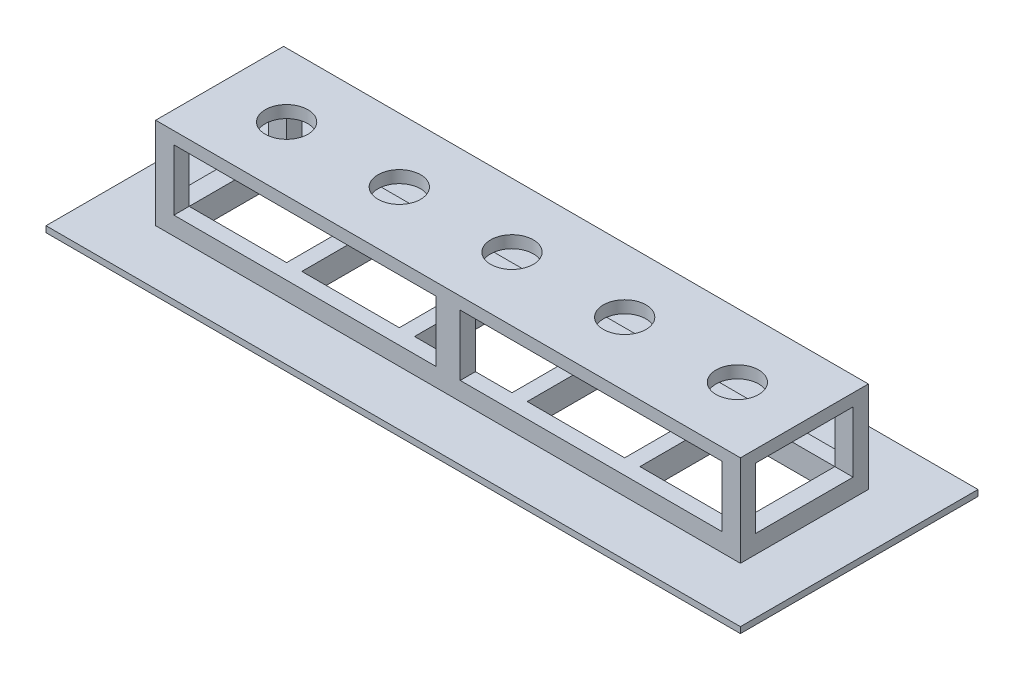
SolidWorks part; units mm, degrees
ref_plane "Front Plane" through (0, 0, 0) normal (0, 0, 1) x (1, 0, 0)
ref_plane "Top Plane" through (0, 0, 0) normal (0, 1, 0) x (1, 0, 0)
ref_plane "Right Plane" through (0, 0, 0) normal (1, 0, 0) x (0, 0, -1)
sketch "Sketch1" plane through (0, 0, 0) normal (0, 1, 0) x (1, 0, 0)
  line L1 (-48, 10.5) -> (48, 10.5)
  line L2 (-48, 10.5) -> (-48, -10.5)
  line L3 (-48, -10.5) -> (48, -10.5)
  line L4 (48, 10.5) -> (48, -10.5)
  line L5 (-48, 10.5) -> (48, -10.5) construction
  line L6 (-48, -10.5) -> (48, 10.5) construction
  point P0 (0, 0)
extrude "Boss-Extrude1" add sketch "Sketch1" along normal blind 3
sketch "Sketch2" plane through (0, 3, 0) normal (0, 1, 0) x (1, 0, 0)
  line L3 (-8, 8) -> (8, 8)
  line L4 (-8, 8) -> (-8, -8)
  line L5 (-45, 8) -> (-29, 8)
  line L6 (-45, 8) -> (-45, -8)
  line L7 (-45, -8) -> (-29, -8)
  line L8 (-29, 8) -> (-29, -8)
  line L9 (-45, 8) -> (-29, -8) construction
  line L10 (-45, -8) -> (-29, 8) construction
  line L11 (-26.5, 8) -> (-10.5, 8)
  line L12 (-26.5, 8) -> (-26.5, -8)
  line L13 (-26.5, -8) -> (-10.5, -8)
  line L14 (-10.5, 8) -> (-10.5, -8)
  line L15 (-26.5, 8) -> (-10.5, -8) construction
  line L16 (-26.5, -8) -> (-10.5, 8) construction
  line L17 (-8, -8) -> (8, -8)
  line L20 (8, 8) -> (8, -8)
  line L21 (-8, 8) -> (8, -8) construction
  line L22 (-8, -8) -> (8, 8) construction
  line L32 (10.5, 8) -> (26.5, 8)
  line L33 (10.5, 8) -> (10.5, -8)
  line L34 (10.5, -8) -> (26.5, -8)
  line L35 (26.5, 8) -> (26.5, -8)
  line L36 (10.5, 8) -> (26.5, -8) construction
  line L37 (10.5, -8) -> (26.5, 8) construction
  line L39 (29, 8) -> (45, 8)
  line L40 (29, 8) -> (29, -8)
  line L41 (29, -8) -> (45, -8)
  line L42 (45, 8) -> (45, -8)
  line L43 (29, 8) -> (45, -8) construction
  line L44 (29, -8) -> (45, 8) construction
  dimension "D1" = 16
  dimension "D2" = 16
  dimension "D3" = 16
  dimension "D4" = 16
  dimension "D5" = 16
  dimension "D6" = 16
  dimension "D7" = 16
  dimension "D8" = 16
  dimension "D9" = 16
  dimension "D10" = 16
extrude "Cut-Extrude3" cut sketch "Sketch2" against normal blind 7 and the other way blind 7
sketch "Sketch5" plane through (0, 3, 0) normal (0, 1, 0) x (1, 0, 0)
  line L0 (-45, 8) -> (-45, 10.5)
  line L1 (48, 10.5) -> (-48, 10.5) construction
  line L2 (-45, -8) -> (-45, -10.5)
  line L4 (-48, -10.5) -> (48, -10.5) construction
  line L5 (-48, 10.5) -> (-45, 10.5)
  line L6 (-48, 10.5) -> (-48, 8)
  line L7 (-48, 8) -> (-45, 8)
  line L8 (-45, 10.5) -> (-45, 8)
  line L9 (-48, 10.5) -> (-45, 8) construction
  line L10 (-48, 8) -> (-45, 10.5) construction
  line L11 (45, 8) -> (45, 10.5)
  line L12 (-48, 10.5) -> (-48, -10.5) construction
  line L13 (45, -8) -> (48, -8)
  line L14 (-48, -8) -> (-45, -8)
  line L15 (-48, -8) -> (-48, -10.5)
  line L16 (-48, -10.5) -> (-45, -10.5)
  line L17 (-45, -8) -> (-45, -10.5)
  line L18 (-48, -8) -> (-45, -10.5) construction
  line L19 (-48, -10.5) -> (-45, -8) construction
  line L20 (48, -10.5) -> (48, 10.5) construction
  line L21 (-8, 8) -> (8, 8) construction
  line L22 (45, 10.5) -> (48, 10.5)
  line L23 (45, 10.5) -> (45, 8)
  line L24 (45, 8) -> (48, 8)
  line L25 (48, 10.5) -> (48, 8)
  line L26 (45, 10.5) -> (48, 8) construction
  line L27 (45, 8) -> (48, 10.5) construction
  line L28 (0, -10.5) -> (0, -8)
  line L29 (45, -8) -> (48, -8)
  line L30 (45, -8) -> (45, -10.5)
  line L31 (45, -10.5) -> (48, -10.5)
  line L32 (48, -8) -> (48, -10.5)
  line L33 (45, -8) -> (48, -10.5) construction
  line L34 (45, -10.5) -> (48, -8) construction
  line L35 (-2, 10.5) -> (2, 10.5)
  line L36 (-2, 10.5) -> (-2, 8)
  line L37 (-2, 8) -> (2, 8)
  line L38 (2, 10.5) -> (2, 8)
  line L39 (-2, 10.5) -> (2, 8) construction
  line L40 (-2, 8) -> (2, 10.5) construction
  line L41 (8, -8) -> (-8, -8) construction
  line L42 (-2, -8) -> (2, -8)
  line L43 (-2, -8) -> (-2, -10.5)
  line L44 (-2, -10.5) -> (2, -10.5)
  line L45 (2, -8) -> (2, -10.5)
  line L46 (-2, -8) -> (2, -10.5) construction
  line L47 (-2, -10.5) -> (2, -8) construction
  point P9 (-46.5, 9.25)
  point P10 (-46.5, -9.25)
  point P21 (46.5, 9.25)
  point P29 (46.5, -9.25)
  point P32 (0, -9.25)
  point P38 (0, 9.25)
  line M37 (48, -10.5) -> (48, 10.5)
  line M38 (48, 10.5) -> (-48, 10.5)
  line M39 (-48, 10.5) -> (-48, -10.5)
  line M40 (-48, -10.5) -> (48, -10.5)
extrude "Boss-Extrude5" add sketch "Sketch5" along normal blind 10 contours L7 L0 M39 M38 | L14 L2 M39 M40 | L11 L24 M37 M38 | L13 L30 M40 M37 | L36 L35 L38 L37 | L43 L42 L45 L44 region at (-46.5, 3, -9.25) region at (-46.5, 3, 9.25) region at (46.5, 3, -9.25) region at (46.5, 3, 9.25)
sketch "Sketch6" plane through (0, 13, 0) normal (0, 1, 0) x (1, 0, 0)
  line L1 (-48, 10.5) -> (48, 10.5)
  line L2 (-48, 10.5) -> (-48, -10.5)
  line L3 (-48, -10.5) -> (48, -10.5)
  line L4 (48, 10.5) -> (48, -10.5)
  line L5 (-48, 10.5) -> (48, -10.5) construction
  line L6 (-48, -10.5) -> (48, 10.5) construction
  point P0 (0, 0)
extrude "Boss-Extrude6" add sketch "Sketch6" along normal blind 2
sketch "Sketch7" plane through (0, 15, 0) normal (0, 1, 0) x (1, 0, 0)
  circle A0 centre (-37, 0) radius 3.5
  circle A1 centre (-18.5, 0) radius 3.5
  circle A2 centre (0, 0) radius 3.5
  circle A3 centre (18.5, 0) radius 3.5
  circle A4 centre (37, 0) radius 3.5
extrude "Cut-Extrude5" cut sketch "Sketch7" against normal blind 2
sketch "Sketch9" plane through (0, 0, 0) normal (0, -1, 0) x (1, 0, 0)
  line L1 (-57, 19.5) -> (57, 19.5)
  line L2 (-57, 19.5) -> (-57, -19.5)
  line L3 (-57, -19.5) -> (57, -19.5)
  line L4 (57, 19.5) -> (57, -19.5)
  line L5 (-57, 19.5) -> (57, -19.5) construction
  line L6 (-57, -19.5) -> (57, 19.5) construction
  point P0 (0, 0)
  dimension "D1" = 114
  dimension "D2" = 39
extrude "Boss-Extrude7" add sketch "Sketch9" along normal blind 1
sketch "Sketch10" plane through (0, -1, 0) normal (0, -1, 0) x (1, 0, 0)
  line L3 (-45, 8) -> (-29, 8)
  line L4 (-45, 8) -> (-45, -8)
  line L5 (-45, -8) -> (-29, -8)
  line L6 (-29, 8) -> (-29, -8)
  line L7 (-45, 8) -> (-29, -8) construction
  line L8 (-45, -8) -> (-29, 8) construction
  line L10 (-26.5, 8) -> (-10.5, 8)
  line L11 (-26.5, 8) -> (-26.5, -8)
  line L12 (-26.5, -8) -> (-10.5, -8)
  line L13 (-10.5, 8) -> (-10.5, -8)
  line L14 (-26.5, 8) -> (-10.5, -8) construction
  line L15 (-26.5, -8) -> (-10.5, 8) construction
  line L17 (-8, 8) -> (8, 8)
  line L18 (-8, 8) -> (-8, -8)
  line L19 (-8, -8) -> (8, -8)
  line L20 (8, 8) -> (8, -8)
  line L21 (-8, 8) -> (8, -8) construction
  line L22 (-8, -8) -> (8, 8) construction
  line L24 (10.5, 8) -> (26.5, 8)
  line L25 (10.5, 8) -> (10.5, -8)
  line L26 (10.5, -8) -> (26.5, -8)
  line L27 (26.5, 8) -> (26.5, -8)
  line L28 (10.5, 8) -> (26.5, -8) construction
  line L29 (10.5, -8) -> (26.5, 8) construction
  line L31 (29, 8) -> (45, 8)
  line L32 (29, 8) -> (29, -8)
  line L33 (29, -8) -> (45, -8)
  line L34 (45, 8) -> (45, -8)
  line L35 (29, 8) -> (45, -8) construction
  line L36 (29, -8) -> (45, 8) construction
  dimension "D1" = 16
  dimension "D2" = 16
  dimension "D3" = 16
  dimension "D4" = 16
  dimension "D5" = 16
  dimension "D6" = 16
  dimension "D7" = 16
  dimension "D8" = 16
  dimension "D9" = 16
  dimension "D10" = 16
extrude "Cut-Extrude6" cut sketch "Sketch10" against normal blind 1
